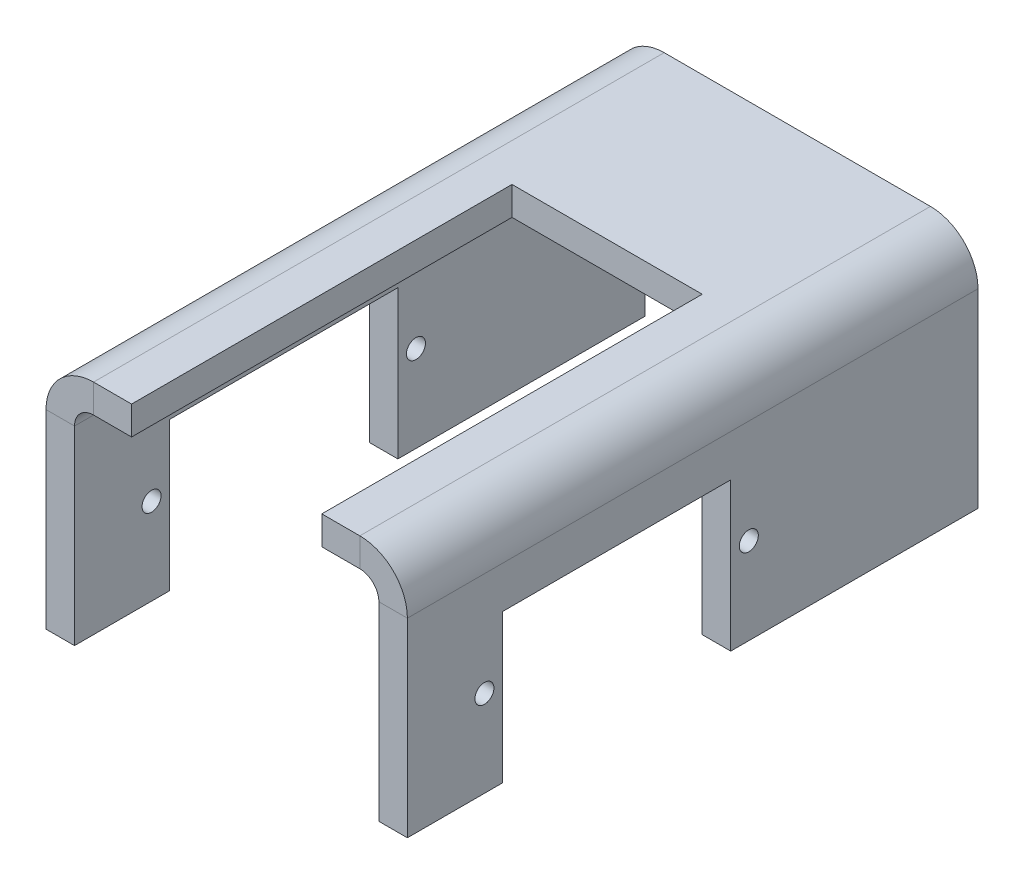
SolidWorks part; units mm, degrees
note: The reader was unsure of these and kept them because the rebuilt part matched: flange length of "Edge-Flange1".
ref_plane "Front Plane" through (0, 0, 0) normal (0, 0, 1) x (1, 0, 0)
ref_plane "Top Plane" through (0, 0, 0) normal (0, 1, 0) x (1, 0, 0)
ref_plane "Right Plane" through (0, 0, 0) normal (1, 0, 0) x (0, 0, -1)
sketch "Sketch1" plane through (0, 0, 0) normal (0, 1, 0) x (1, 0, 0)
  line L1 (-19.5, 10.7919) -> (12.5, 10.7919)
  line L2 (-19.5, 10.7919) -> (-19.5, -49.2081)
  line L3 (-19.5, -49.2081) -> (12.5, -49.2081)
  line L4 (12.5, 10.7919) -> (12.5, -49.2081)
  point P0 (0, 0)
  dimension "D1" = 32
  dimension "D2" = 60
base flange "Base-Flange1" sketch "Sketch1" thickness 3 reverse thickness direction no parameters "D1"=2
edge flange "Edge-Flange1" sketch "Sketch16" flange profiles "Sketch16", "Sketch17" flange angle 90 flange length 25 flange position material outside bend radius 2 thickness 3 relief rectangular parameters "D6"=10, "D8"=1
sketch "Sketch16" plane through (12.5, -3, 0) normal (1, 0, 0) x (0, 0, 1)
  line L2 (-10.7919, 0) -> (-10.7919, 22)
  line L3 (-10.7919, 22) -> (49.2081, 22)
  line L4 (49.2081, 22) -> (49.2081, 0)
  line L19 (49.2081, 0) -> (-10.7919, 0) construction
  line L20 (49.2081, 0) -> (-10.7919, 0)
sketch "Sketch17" plane through (-19.5, -3, 0) normal (-1, 0, 0) x (0, 0, -1)
  line L2 (10.7919, 0) -> (10.7919, 22)
  line L3 (10.7919, 22) -> (-49.2081, 22)
  line L4 (-49.2081, 22) -> (-49.2081, 0)
  line L13 (10.7919, 0) -> (-49.2081, 0) construction
  line L14 (10.7919, 0) -> (-49.2081, 0)
bend "EdgeBend1" bend radius 2 bend angle 90 parameters "D5"=1
bend "EdgeBend2" bend radius 2 bend angle 90 parameters "D5"=2
sketch "Sketch18" plane through (15.5, 0, 0) normal (1, 0, 0) x (0, 0, -1)
  line L0 (-27.2081, -9.3993) -> (-27.2081, -22.3993) construction
  line L1 (-39.2081, -9.3993) -> (-15.2081, -9.3993)
  line L2 (-39.2081, -9.3993) -> (-39.2081, -22.3993)
  line L3 (-39.2081, -22.3993) -> (-15.2081, -22.3993)
  line L4 (-15.2081, -9.3993) -> (-15.2081, -22.3993)
  line L5 (-39.2081, -9.3993) -> (-15.2081, -22.3993) construction
  line L6 (-39.2081, -22.3993) -> (-15.2081, -9.3993) construction
  line L7 (-49.2081, -5) -> (-49.2081, -25) construction
  circle A0 centre (-41.1081, -15.8993) radius 1
  circle A1 centre (-13.3081, -15.8993) radius 1
  point P12 (-27.2081, -15.8993)
  point P14 (-27.2081, -15.8993)
  dimension "D1" = 2
  dimension "D2" = 27.8
  dimension "D3" = 24
  dimension "D4" = 13
  dimension "D5" = 10
extrude "Cut-Extrude1" cut sketch "Sketch18" against normal through all normal cut yes
sketch "Sketch19" plane through (0, 0, 0) normal (0, 1, 0) x (1, 0, 0)
  line L5 (-3.5, 10.7919) -> (-3.5, -49.2081) construction
  line L6 (10.5, 10.7919) -> (-17.5, 10.7919) construction
  line L7 (-17.5, -49.2081) -> (10.5, -49.2081) construction
  line L10 (-13.5, -9.2081) -> (6.5, -9.2081)
  line L11 (-13.5, -9.2081) -> (-13.5, -49.2081)
  line L12 (-13.5, -49.2081) -> (6.5, -49.2081)
  line L13 (6.5, -9.2081) -> (6.5, -49.2081)
  line L14 (-13.5, -9.2081) -> (6.5, -49.2081) construction
  line L15 (-13.5, -49.2081) -> (6.5, -9.2081) construction
  point P10 (-3.5, -29.2081)
  dimension "D1" = 20
  dimension "D2" = 40
extrude "Cut-Extrude2" cut sketch "Sketch19" against normal through all normal cut yes
sketch "Sketch20" plane through (15.5, 0, 0) normal (1, 0, 0) x (0, 0, -1)
  line L0 (-49.2081, -25) -> (10.7919, -25) construction
  line L1 (-39.2081, -22.3993) -> (-15.2081, -22.3993)
  line L2 (-39.2081, -22.3993) -> (-39.2081, -25)
  line L3 (-39.2081, -25) -> (-15.2081, -25)
  line L4 (-15.2081, -22.3993) -> (-15.2081, -25)
  line L5 (-39.2081, -22.3993) -> (-15.2081, -25) construction
  line L6 (-39.2081, -25) -> (-15.2081, -22.3993) construction
  line L7 (-15.2081, -22.3993) -> (-15.2081, -9.3993) construction
  point P4 (-27.2081, -23.6996)
extrude "Cut-Extrude3" cut sketch "Sketch20" against normal through all normal cut yes
sketch "Bend-Lines3" [suppressed] plane through (0, 0, 0) normal (0, 1, 0) x (1, 0, 0)
sketch "Bounding-Box3" [suppressed] plane through (0, 0, 0) normal (0, 1, 0) x (1, 0, 0)
sheet metal parameters "Sheet-Metal3" thickness 3 parameters "D1"=2
flat pattern "Flat-Pattern3" [suppressed]
sketch "Bend-Lines4" plane through (0, 0, 0) normal (0, 1, 0) x (1, 0, 0)
sketch3d "Bounding-Box4" [suppressed]
  line L0 (39.5626, -34.1565, 0) -> (-39.5626, -34.1565, 0) construction
  line L1 (39.5626, 34.1565, 0) -> (-39.5626, 34.1565, 0) construction
  line L2 (39.5626, -34.1565, 0) -> (39.5626, 34.1565, 0) construction
  line L3 (-39.5626, -34.1565, 0) -> (-39.5626, 34.1565, 0) construction
sheet metal parameters "Sheet-Metal4" thickness 3 parameters "D1"=2
flat pattern "Flat-Pattern3" [suppressed]
sketch "Bend-Lines4" plane through (0, 0, 0) normal (0, 1, 0) x (1, 0, 0)
  line L0 (-13.2489, 10.7919) -> (-13.2489, -89.2081) construction
  line L1 (13.2489, -89.2081) -> (13.2489, 10.7919) construction
  line L2 (-13.2489, 10.7919) -> (-13.2489, -89.2081) construction
  line L3 (13.2489, -89.2081) -> (13.2489, 10.7919) construction
sketch3d "Bounding-Box4" [suppressed]
  line L0 (-35.9978, 10.7919, 0) -> (-35.9978, -89.2081, 0) construction
  line L1 (35.9978, 10.7919, 0) -> (35.9978, -89.2081, 0) construction
  line L2 (-35.9978, 10.7919, 0) -> (35.9978, 10.7919, 0) construction
  line L3 (-35.9978, -89.2081, 0) -> (35.9978, -89.2081, 0) construction
bend of the flat pattern "Flatten-<EdgeBend1>1"
bend of the flat pattern "Flatten-<EdgeBend2>1"
sketch "Sketch18-1" plane through (10.9978, 0, 0) normal (0, 1, 0) x (0, 0, -1)
  line L1 (-25.1449, -6.968) -> (-1.1449, -6.968)
  line L2 (-25.1449, -6.968) -> (-25.1449, -19.968)
  line L3 (-25.1449, -19.968) -> (-1.1449, -19.968)
  line L4 (-1.1449, -6.968) -> (-1.1449, -19.968)
  line L5 (-25.1449, -6.968) -> (-1.1449, -19.968) construction
  line L6 (-25.1449, -19.968) -> (-1.1449, -6.968) construction
  circle A0 centre (-25.6827, -12.1911) radius 1
  circle A1 centre (-0.3827, -12.1911) radius 1
  point P12 (-13.1449, -13.468)
  dimension "D1" = 2
  dimension "D2" = 25.3
  dimension "D3" = 24
  dimension "D4" = 13
sheet metal parameters "Sheet-Metal5" thickness 3 parameters "D1"=2
flat pattern "Flat-Pattern3" [suppressed]
sketch "Bend-Lines4" plane through (0, 0, 0) normal (0, 1, 0) x (1, 0, 0)
  line L0 (-20.2489, 10.7919) -> (-20.2489, -39.2081) construction
  line L1 (13.2489, -39.2081) -> (13.2489, 10.7919) construction
  line L2 (-20.2489, 10.7919) -> (-20.2489, -39.2081) construction
  line L3 (13.2489, -39.2081) -> (13.2489, 10.7919) construction
sketch3d "Bounding-Box4" [suppressed]
  line L0 (35.9978, -39.2081, 0) -> (-42.9978, -39.2081, 0) construction
  line L1 (35.9978, 10.7919, 0) -> (-42.9978, 10.7919, 0) construction
  line L2 (35.9978, -39.2081, 0) -> (35.9978, 10.7919, 0) construction
  line L3 (-42.9978, -39.2081, 0) -> (-42.9978, 10.7919, 0) construction
bend of the flat pattern "Flatten-<EdgeBend1>1"
bend of the flat pattern "Flatten-<EdgeBend2>1"
sketch "Sketch18-1" plane through (10.9978, 0, 0) normal (0, 1, 0) x (0, 0, -1)
  line L0 (-11.6725, -9.3993) -> (-11.6725, -22.3993) construction
  line L1 (-23.6725, -9.3993) -> (0.3275, -9.3993)
  line L2 (-23.6725, -9.3993) -> (-23.6725, -22.3993)
  line L3 (-23.6725, -22.3993) -> (0.3275, -22.3993)
  line L4 (0.3275, -9.3993) -> (0.3275, -22.3993)
  line L5 (-23.6725, -9.3993) -> (0.3275, -22.3993) construction
  line L6 (-23.6725, -22.3993) -> (0.3275, -9.3993) construction
  circle A0 centre (-25.5725, -15.8993) radius 1
  circle A1 centre (2.2275, -15.8993) radius 1
  point P12 (-11.6725, -15.8993)
  point P14 (-11.6725, -15.8993)
  dimension "D1" = 2
  dimension "D2" = 27.8
  dimension "D3" = 24
  dimension "D4" = 13
sheet metal parameters "Sheet-Metal6" thickness 3 parameters "D1"=2
flat pattern "Flat-Pattern3" [suppressed]
sketch "Bend-Lines4" plane through (0, 0, 0) normal (0, 1, 0) x (1, 0, 0)
  line L0 (-20.2489, 10.7919) -> (-20.2489, -49.2081) construction
  line L1 (13.2489, -49.2081) -> (13.2489, 10.7919) construction
  line L2 (-20.2489, 10.7919) -> (-20.2489, -49.2081) construction
  line L3 (13.2489, -49.2081) -> (13.2489, 10.7919) construction
sketch3d "Bounding-Box4" [suppressed]
  line L0 (35.9978, -49.2081, 0) -> (-42.9978, -49.2081, 0) construction
  line L1 (35.9978, 10.7919, 0) -> (-42.9978, 10.7919, 0) construction
  line L2 (35.9978, -49.2081, 0) -> (35.9978, 10.7919, 0) construction
  line L3 (-42.9978, -49.2081, 0) -> (-42.9978, 10.7919, 0) construction
bend of the flat pattern "Flatten-<EdgeBend1>1"
bend of the flat pattern "Flatten-<EdgeBend2>1"
sketch "Sketch18-1" plane through (10.9978, 0, 0) normal (0, 1, 0) x (0, 0, -1)
  line L0 (-27.2081, -9.3993) -> (-27.2081, -22.3993) construction
  line L1 (-39.2081, -9.3993) -> (-15.2081, -9.3993)
  line L2 (-39.2081, -9.3993) -> (-39.2081, -22.3993)
  line L3 (-39.2081, -22.3993) -> (-15.2081, -22.3993)
  line L4 (-15.2081, -9.3993) -> (-15.2081, -22.3993)
  line L5 (-39.2081, -9.3993) -> (-15.2081, -22.3993) construction
  line L6 (-39.2081, -22.3993) -> (-15.2081, -9.3993) construction
  line L7 (-49.2081, 5.4978) -> (-49.2081, -25) construction
  circle A0 centre (-41.1081, -15.8993) radius 1
  circle A1 centre (-13.3081, -15.8993) radius 1
  point P12 (-27.2081, -15.8993)
  point P14 (-27.2081, -15.8993)
  dimension "D1" = 2
  dimension "D2" = 27.8
  dimension "D3" = 24
  dimension "D4" = 13
  dimension "D5" = 10
sheet metal parameters "Sheet-Metal7" thickness 3 parameters "D1"=2
flat pattern "Flat-Pattern3" [suppressed]
sketch "Bend-Lines4" plane through (0, 0, 0) normal (0, 1, 0) x (1, 0, 0)
  line L0 (-20.2489, 10.7919) -> (-20.2489, -49.2081) construction
  line L1 (13.2489, -49.2081) -> (13.2489, 10.7919) construction
  line L2 (-20.2489, 10.7919) -> (-20.2489, -49.2081) construction
  line L3 (13.2489, -49.2081) -> (13.2489, 10.7919) construction
sketch3d "Bounding-Box4" [suppressed]
  line L0 (35.9978, -49.2081, 0) -> (-42.9978, -49.2081, 0) construction
  line L1 (35.9978, 10.7919, 0) -> (-42.9978, 10.7919, 0) construction
  line L2 (35.9978, -49.2081, 0) -> (35.9978, 10.7919, 0) construction
  line L3 (-42.9978, -49.2081, 0) -> (-42.9978, 10.7919, 0) construction
bend of the flat pattern "Flatten-<EdgeBend1>1"
bend of the flat pattern "Flatten-<EdgeBend2>1"
sketch "Sketch18-1" [suppressed] plane through (10.9978, 0, 0) normal (0, 1, 0) x (0, 0, -1)
  line L0 (-27.2081, -9.3993) -> (-27.2081, -22.3993) construction
  line L1 (-39.2081, -9.3993) -> (-15.2081, -9.3993)
  line L2 (-39.2081, -9.3993) -> (-39.2081, -22.3993)
  line L3 (-39.2081, -22.3993) -> (-15.2081, -22.3993)
  line L4 (-15.2081, -9.3993) -> (-15.2081, -22.3993)
  line L5 (-39.2081, -9.3993) -> (-15.2081, -22.3993) construction
  line L6 (-39.2081, -22.3993) -> (-15.2081, -9.3993) construction
  line L7 (-49.2081, 4.4978) -> (-49.2081, -25) construction
  circle A0 centre (-41.1081, -15.8993) radius 1
  circle A1 centre (-13.3081, -15.8993) radius 1
  point P12 (-27.2081, -15.8993)
  point P14 (-27.2081, -15.8993)
  dimension "D1" = 2
  dimension "D2" = 27.8
  dimension "D3" = 24
  dimension "D4" = 13
  dimension "D5" = 10
